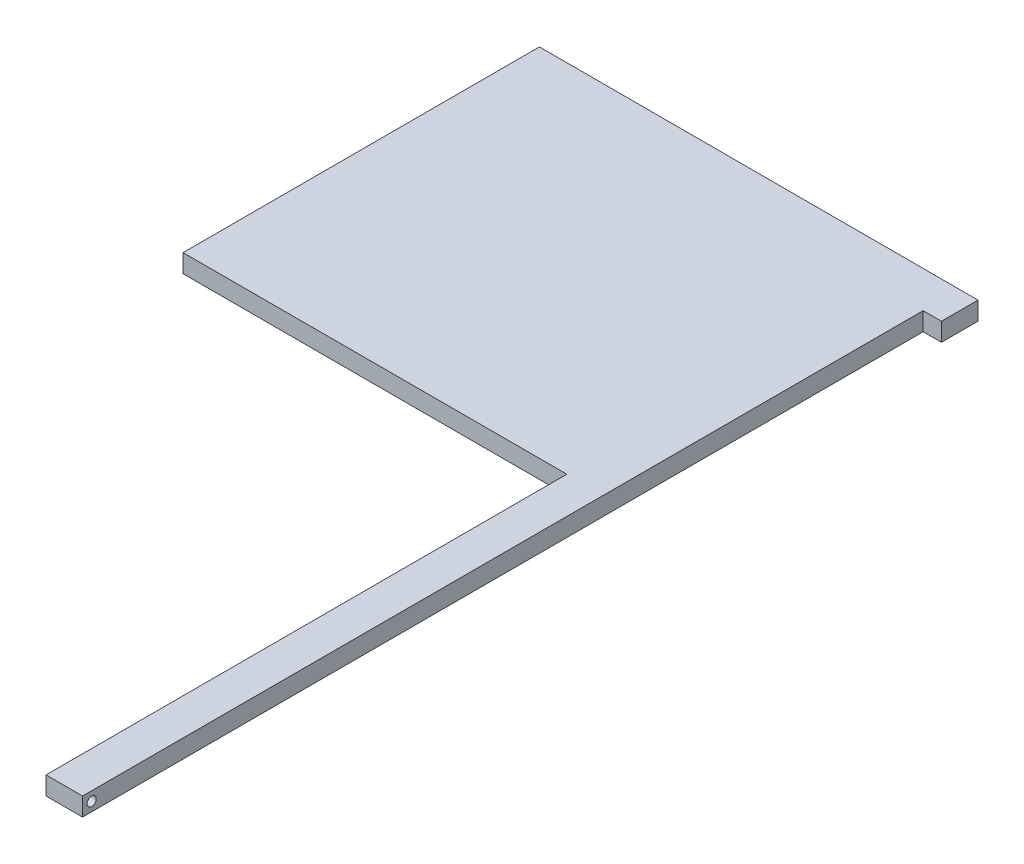
SolidWorks part; units mm, degrees
other "Markup1"
sketch "Sketch12" plane through (250.825, 22.225, 158.75) normal (0.1153, 0.0728, 0.9907) x (0.9687, -0.2289, -0.0959)
material "6061 Alloy"
ref_plane "Front Plane" through (0, 0, 0) normal (0, 0, 1) x (1, 0, 0)
ref_plane "Top Plane" through (0, 0, 0) normal (0, 1, 0) x (1, 0, 0)
ref_plane "Right Plane" through (0, 0, 0) normal (1, 0, 0) x (0, 0, -1)
sketch "Sketch1" plane through (0, 0, 0) normal (0, 1, 0) x (1, 0, 0)
  line L1 (-241.3, 152.4) -> (241.3, 152.4)
  line L2 (-241.3, 152.4) -> (-241.3, -152.4)
  line L3 (-241.3, -152.4) -> (241.3, -152.4)
  line L4 (241.3, 152.4) -> (241.3, -152.4)
  line L5 (-241.3, 152.4) -> (241.3, -152.4) construction
  line L6 (-241.3, -152.4) -> (241.3, 152.4) construction
  point P0 (0, 0)
  dimension "D1" = 482.6
  dimension "D2" = 304.8
extrude "Boss-Extrude1" add sketch "Sketch1" along normal blind 12.7
sketch "Sketch2" plane through (0, 12.7, 0) normal (0, 1, 0) x (1, 0, 0)
  line L0 (-241.3, -152.4) -> (241.3, -152.4) construction
  line L1 (-241.3, 152.4) -> (-228.6, 152.4)
  line L2 (-241.3, 152.4) -> (-241.3, -152.4)
  line L3 (-241.3, -152.4) -> (-228.6, -152.4)
  line L4 (-228.6, 28.575) -> (-228.6, -152.4)
  line L5 (241.3, 152.4) -> (-241.3, 152.4) construction
  line L6 (241.3, 152.4) -> (228.6, 152.4)
  line L7 (241.3, 152.4) -> (241.3, -152.4)
  line L8 (241.3, -152.4) -> (228.6, -152.4)
  line L9 (228.6, 28.575) -> (228.6, -152.4)
  line L10 (-228.6, 152.4) -> (228.6, 152.4)
  line L12 (-228.6, 28.575) -> (228.6, 28.575)
  point P14 (-234.95, -152.4)
  dimension "D1" = 12.7
  dimension "D2" = 180.975
extrude "Boss-Extrude2" add sketch "Sketch2" along normal blind 6.35
sketch "Sketch3" plane through (-241.3, 0, 0) normal (-1, 0, 0) x (0, 0, 1)
  line L0 (152.4, 19.05) -> (152.4, 0) construction
  line L1 (-152.4, 19.05) -> (152.4, 19.05) construction
  circle A0 centre (149.225, 15.875) radius 1.5875
  dimension "D3" = 3.175
  dimension "D1" = 3.175
  dimension "D2" = 3.175
extrude "Cut-Extrude1" cut sketch "Sketch3" against normal through all
sketch "Sketch4" plane through (0, 0, 152.4) normal (0, 0, 1) x (1, 0, 0)
  line L0 (-241.3, 19.05) -> (-241.3, 0) construction
  line L1 (-241.3, 12.7) -> (-247.65, 12.7)
  line L2 (-241.3, 12.7) -> (-241.3, 0)
  line L3 (-241.3, 0) -> (-247.65, 0)
  line L4 (-247.65, 12.7) -> (-247.65, 0)
  line L5 (-241.3, 0) -> (241.3, 0) construction
  dimension "D1" = 12.7
  dimension "D2" = 6.35
extrude "Boss-Extrude3" add sketch "Sketch4" against normal blind 292.1
sketch "Sketch5" plane through (-241.3, 0, 0) normal (-1, 0, 0) x (0, 0, 1)
  line L0 (-152.4, 0) -> (-139.7, 0) construction
  line L1 (-152.4, 19.05) -> (-139.7, 19.05)
  line L2 (-152.4, 19.05) -> (-152.4, 0)
  line L3 (-152.4, 0) -> (-139.7, 0)
  line L4 (-139.7, 19.05) -> (-139.7, 0)
  line L5 (-139.7, 0) -> (-139.7, 12.7) construction
extrude "Boss-Extrude4" add sketch "Sketch5" along normal up to surface (6.35 mm away) up to face at (-247.65, 6.35, 6.35)
mirror "Mirror1" about plane through (0, 0, 0) normal (1, 0, 0) of "Boss-Extrude4", "Boss-Extrude3"
sketch "Sketch6" plane through (-241.3, 0, 0) normal (-1, 0, 0) x (0, 0, 1)
  line L0 (147.32, 6.35) -> (128.27, 6.35) construction
  line L1 (147.32, 2.54) -> (128.27, 2.54)
  line L2 (147.32, 10.16) -> (128.27, 10.16)
  line L3 (152.4, 19.05) -> (152.4, 12.7) construction
  line L5 (152.4, 12.7) -> (152.4, 0) construction
  arc A0 (147.32, 2.54) -> (147.32, 10.16) centre (147.32, 6.35) ccw
  arc A1 (128.27, 10.16) -> (128.27, 2.54) centre (128.27, 6.35) ccw
  point P2 (137.795, 6.35)
  point P11 (152.4, 6.35)
  dimension "D1" = 19.05
  dimension "D2" = 5.08
  dimension "D3" = 7.62
extrude "Cut-Extrude2" cut sketch "Sketch6" against normal blind 25.4 from surface starting at face at (-247.65, 10.5833, -46.5667)
extrude "Cut-Extrude3" cut sketch "Sketch6<2>" along normal blind 25.4 from surface starting at face at (247.65, 10.5833, -46.5667)
sketch "Sketch6<2>" plane through (-241.3, 0, 0) normal (-1, 0, 0) x (0, 0, 1) same geometry as "Sketch6"
sketch "Sketch11" plane through (0, 0, 0) normal (0, -1, 0) x (1, 0, 0)
  line L0 (-247.65, 124.46) -> (-222.25, 124.46)
  line L1 (-222.25, 124.46) -> (-222.25, 140.97)
  line L2 (-222.25, 140.97) -> (-247.65, 124.46)
  line L3 (-222.25, 128.27) -> (-222.25, 147.32) construction
  dimension "D1" = 10.16
extrude "Boss-Extrude5" add sketch "Sketch11" against normal up to surface (10.16 mm away) from surface up to face at (-234.95, 10.16, 137.795) starting at face at (-234.95, 2.54, 137.795)
mirror "Mirror2" about plane through (0, 0, 0) normal (1, 0, 0) of "Boss-Extrude5"
sketch "Sketch13" plane through (-247.65, 0, 0) normal (-1, 0, 0) x (0, 0, 1)
  line L1 (152.4, 12.7) -> (-152.4, 12.7)
  line L2 (152.4, 12.7) -> (152.4, 0)
  line L3 (152.4, 0) -> (-152.4, 0)
  line L4 (-152.4, 12.7) -> (-152.4, 0)
extrude "Cut-Extrude4" cut sketch "Sketch13" against normal through all
sketch "Sketch14" plane through (0, 19.05, 0) normal (0, 1, 0) x (1, 0, 0)
  line L0 (-95.25, 152.4) -> (-95.25, 28.575)
  line L1 (247.65, 152.4) -> (-247.65, 152.4) construction
  line L2 (-228.6, 28.575) -> (228.6, 28.575) construction
  line L3 (95.25, 152.4) -> (95.25, 28.575)
  line L5 (-95.25, 28.575) -> (95.25, 28.575) construction
  point P8 (0, 28.575)
  dimension "D1" = 190.5
sketch "Sketch15" [suppressed] plane through (0, 19.05, 0) normal (0, 1, 0) x (1, 0, 0)
  line L1 (-88.9, 152.4) -> (293.6384, 152.4)
  line L2 (-88.9, 152.4) -> (-88.9, -195.5)
  line L3 (-88.9, -195.5) -> (293.6384, -195.5)
  line L4 (293.6384, 152.4) -> (293.6384, -195.5)
extrude "Cut-Extrude5" [suppressed] cut sketch "Sketch15" against normal through all
sketch "Sketch16" [suppressed] plane through (0, 19.05, 0) normal (0, 1, 0) x (1, 0, 0)
  line L1 (-95.25, 152.4) -> (-297.2636, 152.4)
  line L2 (-95.25, 152.4) -> (-95.25, -161.8378)
  line L3 (-95.25, -161.8378) -> (-297.2636, -161.8378)
  line L4 (-297.2636, 152.4) -> (-297.2636, -161.8378)
  line L5 (95.25, 152.4) -> (291.049, 152.4)
  line L6 (95.25, 152.4) -> (95.25, -177.3742)
  line L7 (95.25, -177.3742) -> (291.049, -177.3742)
  line L8 (291.049, 152.4) -> (291.049, -177.3742)
extrude "Cut-Extrude6" [suppressed] cut sketch "Sketch16" against normal through all
sketch "Sketch17" plane through (0, 19.05, 0) normal (0, 1, 0) x (1, 0, 0)
  line L1 (95.25, 152.4) -> (-273.959, 152.4)
  line L2 (95.25, 152.4) -> (95.25, -155.6232)
  line L3 (95.25, -155.6232) -> (-273.959, -155.6232)
  line L4 (-273.959, 152.4) -> (-273.959, -155.6232)
extrude "Cut-Extrude7" cut sketch "Sketch17" against normal through all
